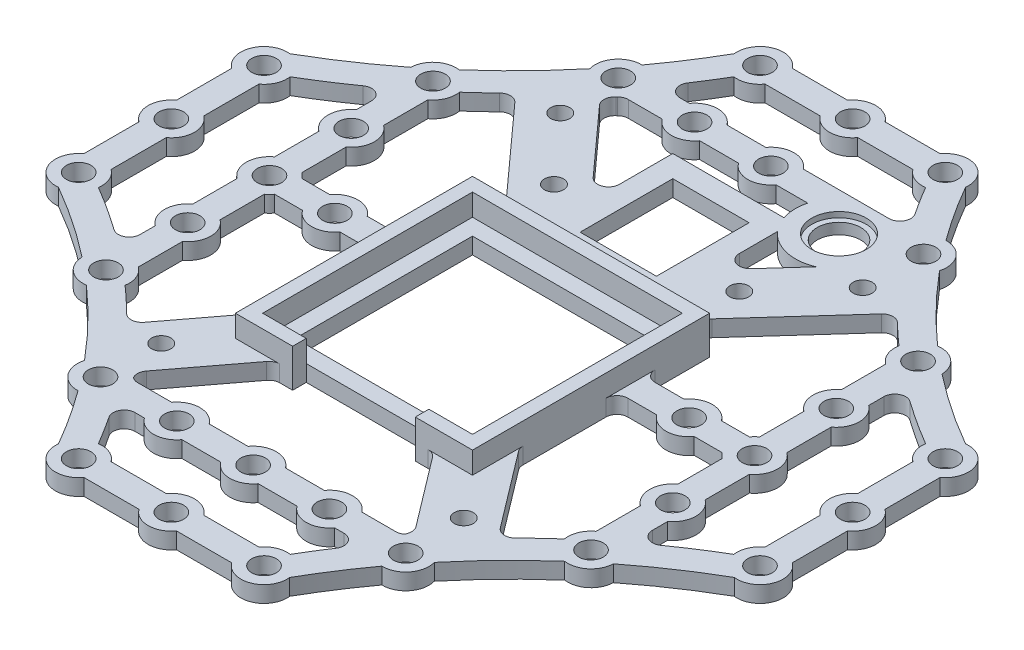
SolidWorks part; units mm, degrees
ref_plane "Front Plane" through (0, 0, 0) normal (0, 0, 1) x (1, 0, 0)
ref_plane "Top Plane" through (0, 0, 0) normal (0, 1, 0) x (1, 0, 0)
ref_plane "Right Plane" through (0, 0, 0) normal (1, 0, 0) x (0, 0, -1)
sketch "Sketch1" plane through (0, 0, 0) normal (0, 1, 0) x (1, 0, 0)
  line L0 (-32, 0) -> (32, 0) construction
  line L1 (-32, 41) -> (32, 41)
  line L2 (-32, 41) -> (-32, -41)
  line L3 (-32, -41) -> (32, -41)
  line L4 (32, 41) -> (32, -41)
  line L5 (-32, 41) -> (32, -41) construction
  line L6 (-32, -41) -> (32, 41) construction
  line L7 (0, 41) -> (0, -41) construction
  circle A0 centre (27.75, -36.6) radius 1.75
  circle A1 centre (-27.75, -36.6) radius 1.75
  circle A2 centre (27.75, 36.6) radius 1.75
  circle A3 centre (-27.75, 36.6) radius 1.75
  point P0 (0, 0)
  dimension "D3" = 3.5
  dimension "D1" = 64
  dimension "D2" = 82
  dimension "D4" = 27.75
  dimension "D5" = 36.6
extrude "Boss-Extrude1" add sketch "Sketch1" along normal blind 3
sketch "Sketch2" plane through (0, 3, 0) normal (0, 1, 0) x (1, 0, 0)
  line L0 (0, 41) -> (0, -41) construction
  line L1 (32, 41) -> (-32, 41) construction
  line L2 (-32, -41) -> (32, -41) construction
  line L3 (-32, 0) -> (32, 0) construction
  line L4 (-32, 41) -> (-32, -41) construction
  line L5 (32, -41) -> (32, 41) construction
  line L6 (-11.25, -26.5) -> (-11.25, -29)
  line L7 (-19.25, 12) -> (19.25, 12)
  line L8 (-19.25, 12) -> (-19.25, -26.5)
  line L9 (-19.25, -26.5) -> (-11.25, -26.5)
  line L10 (19.25, 12) -> (19.25, -26.5)
  line L11 (-19.25, 12) -> (19.25, -26.5) construction
  line L12 (-19.25, -26.5) -> (19.25, 12) construction
  line L13 (-21.75, 14.5) -> (21.75, 14.5)
  line L14 (-21.75, 14.5) -> (-21.75, -29)
  line L15 (-21.75, -29) -> (-11.25, -29)
  line L16 (21.75, 14.5) -> (21.75, -29)
  line L17 (-21.75, 14.5) -> (21.75, -29) construction
  line L18 (-21.75, -29) -> (21.75, 14.5) construction
  line L19 (11.25, -26.5) -> (11.25, -29)
  line L20 (11.25, -26.5) -> (19.25, -26.5)
  line L21 (11.25, -29) -> (21.75, -29)
  point P12 (0, -7.25)
  point P17 (0, -7.25)
  point P19 (0, -7.25)
  dimension "D1" = 38.5
  dimension "D2" = 2.5
  dimension "D3" = 12
  dimension "D4" = 8
  dimension "D5" = 8
extrude "GPS-Housing" add sketch "Sketch2" along normal blind 4
sketch "Sketch3" plane through (0, 3, 0) normal (0, 1, 0) x (1, 0, 0)
  line L0 (-32, 24.7) -> (32, 24.7) construction
  line L1 (-32, 41) -> (-32, -41) construction
  line L2 (32, -41) -> (32, 41) construction
  line L3 (0, 41) -> (0, 6.6316) construction
  line L6 (21.75, 14.5) -> (-21.75, 14.5) construction
  line L7 (32, 41) -> (-32, 41) construction
  circle A0 centre (-17, 24.7) radius 1.75
  circle A1 centre (17, 24.7) radius 1.75
  dimension "D1" = 3.5
  dimension "D2" = 10.2
  dimension "D3" = 17
extrude "Spectrum-Cover-Hole" cut sketch "Sketch3" against normal through all
sketch "Sketch6" plane through (0, 3, 0) normal (0, 1, 0) x (1, 0, 0)
  line L0 (0, 41) -> (0, -41) construction
  line L1 (32, 41) -> (-32, 41) construction
  line L2 (-32, -41) -> (32, -41) construction
  line L3 (-32, 0) -> (32, 0) construction
  line L4 (-32, 41) -> (-32, -41) construction
  line L5 (32, -41) -> (32, 41) construction
  line L6 (0, 0) -> (116.6726, -116.6726) construction
  line L7 (0, -41) -> (0, -155.7646) construction
  line L8 (32, 0) -> (119.0429, 0) construction
  line L9 (65, 19.5647) -> (65, -19.5647)
  line L10 (-19.5647, -65) -> (19.5647, -65)
  line L11 (-65, 19.5647) -> (-65, -19.5647)
  line L12 (-19.5647, 65) -> (19.5647, 65)
  line L14 (-32, 41) -> (32, 41)
  line L15 (32, 41) -> (32, -41)
  line L16 (32, -41) -> (-32, -41)
  line L17 (-32, -41) -> (-32, 41)
  arc A0 (65, -19.5647) -> (19.5647, -65) centre (116.6726, -116.6726) ccw
  circle A1 centre (116.6726, -116.6726) radius 110 construction
  arc A2 (-65, -19.5647) -> (-19.5647, -65) centre (-116.6726, -116.6726) cw
  arc A3 (65, 19.5647) -> (19.5647, 65) centre (116.6726, 116.6726) cw
  arc A4 (-65, 19.5647) -> (-19.5647, 65) centre (-116.6726, 116.6726) ccw
  point P24 (0, -65)
  point P28 (116.6726, -116.6726)
  point P30 (65, 0)
  point P36 (-65, 0)
  dimension "D9" = 220
  dimension "D1" = 45
  dimension "D2" = 65
  dimension "D3" = 65
  dimension "D4" = 165
extrude "Extension" add sketch "Sketch6" against normal blind 3
sketch "Sketch7" plane through (0, 3, 0) normal (0, 1, 0) x (1, 0, 0)
  line L1 (65, 0) -> (-65, 0) construction
  line L2 (65, -19.5647) -> (65, 19.5647) construction
  line L3 (-65, 19.5647) -> (-65, -19.5647) construction
  line L4 (0, 65) -> (0, -65) construction
  line L5 (19.5647, 65) -> (-19.5647, 65) construction
  line L6 (-19.5647, -65) -> (19.5647, -65) construction
  line L8 (0, -60) -> (16.6066, -60)
  line L9 (60, -19.5647) -> (60, 19.5647)
  line L10 (60, -16.6066) -> (60, 0)
  line L11 (-60, 0) -> (-60, -16.6066)
  line L12 (-16.6066, -60) -> (0, -60)
  line L13 (0, 60) -> (-16.6066, 60)
  line L14 (-60, 16.6066) -> (-60, 0)
  line L15 (60, 0) -> (60, 16.6066)
  line L16 (16.6066, 60) -> (0, 60)
  line L18 (47, 25.1809) -> (47, -25.1809)
  line L19 (42, 29.2141) -> (42, -29.2141)
  line L20 (21.75, -20.4107) -> (34.0707, -36.6606)
  line L21 (60, 2.5) -> (60, -2.5)
  line L24 (0, 0) -> (27.75, -36.6) construction
  line L25 (21.75, -29) -> (21.75, 14.5) construction
  line L26 (14.608, -29) -> (26.7391, -45)
  line L27 (11.25, -29) -> (21.75, -29) construction
  line L28 (-22.9722, -50) -> (22.9722, -50)
  line L29 (-26.7391, -45) -> (26.7391, -45)
  line L30 (-10.8771, 43.5) -> (12.4237, 43.5) construction
  line L31 (21.75, 14.5) -> (-21.75, 14.5) construction
  line L32 (-47, 25.1809) -> (-47, -25.1809)
  line L33 (-42, 29.2141) -> (-42, -29.2141)
  line L34 (-21.75, -20.4107) -> (-34.0707, -36.6606)
  line L35 (-14.608, -29) -> (-26.7391, -45)
  line L36 (15.8714, 14.5) -> (35.0176, 35.6944)
  line L37 (-15.8714, 14.5) -> (-35.0176, 35.6944)
  line L38 (-22.9722, 50) -> (22.9722, 50)
  line L39 (-7, 36.5) -> (7, 36.5)
  line L40 (-7, 36.5) -> (-7, 19.5)
  line L41 (-7, 19.5) -> (7, 19.5)
  line L42 (7, 36.5) -> (7, 19.5)
  line L43 (-7, 36.5) -> (7, 19.5) construction
  line L44 (-7, 19.5) -> (7, 36.5) construction
  line L45 (-26.7391, 45) -> (26.7391, 45)
  line L46 (-19.25, 12) -> (19.25, 12) construction
  line L47 (-16.25, 9) -> (16.25, 9)
  line L48 (-16.25, 9) -> (-16.25, -23.5)
  line L49 (-16.25, -23.5) -> (-11.25, -23.5)
  line L50 (16.25, 9) -> (16.25, -23.5)
  line L51 (-19.25, -26.5) -> (-19.25, 12) construction
  line L52 (19.25, 12) -> (19.25, -26.5) construction
  line L53 (19.25, -26.5) -> (11.25, -26.5) construction
  line L54 (-11.25, -29) -> (-11.25, -23.5)
  line L55 (11.25, -29) -> (11.25, -23.5)
  line L57 (11.25, -23.5) -> (16.25, -23.5)
  line L58 (-21.75, 14.5) -> (-21.75, -29) construction
  line L59 (-42, 2.5) -> (-21.75, 2.5)
  line L60 (-42, 2.5) -> (-42, -2.5)
  line L61 (-42, -2.5) -> (-21.75, -2.5)
  line L62 (-21.75, 2.5) -> (-21.75, -2.5)
  line L63 (42, -2.5) -> (21.75, -2.5)
  line L64 (42, 2.5) -> (21.75, 2.5)
  line L65 (21.75, 14.5) -> (-21.75, 14.5) construction
  line L66 (27.75, 36.6) -> (17, 24.7) construction
  line L67 (15.8714, 14.5) -> (21.75, 14.5)
  line L68 (21.75, 14.5) -> (21.75, 2.5)
  line L69 (-15.8714, 14.5) -> (-21.75, 14.5)
  line L70 (-21.75, 14.5) -> (-21.75, 2.5)
  line L71 (-11.25, -23.5) -> (11.25, -23.5)
  line L72 (-11.25, -26.5) -> (11.25, -26.5)
  arc A6 (62.6512, -15.1507) -> (15.1507, -62.6512) centre (116.6726, -116.6726) ccw
  arc A7 (60, -16.6066) -> (16.6066, -60) centre (116.6726, -116.6726) ccw
  arc A8 (-16.6066, -60) -> (-60, -16.6066) centre (-116.6726, -116.6726) ccw
  arc A9 (-60, 16.6066) -> (-16.6066, 60) centre (-116.6726, 116.6726) ccw
  arc A10 (16.6066, 60) -> (60, 16.6066) centre (116.6726, 116.6726) ccw
  point P45 (0, 0)
  point P73 (0, 28)
  line M3 (21.75, 14.5) -> (21.75, -29)
  line M4 (21.75, -29) -> (11.25, -29)
  line M5 (11.25, -29) -> (11.25, -26.5)
  line M11 (-11.25, -26.5) -> (-11.25, -29)
  line M12 (-11.25, -29) -> (-21.75, -29)
  line M13 (-21.75, -29) -> (-21.75, 14.5)
  line M20 (-21.75, 14.5) -> (21.75, 14.5)
  dimension "D1" = 5
  dimension "D4" = 2.5
  dimension "D2" = 42
  dimension "D3" = 5
  dimension "D5" = 10
  dimension "D8" = 5
  dimension "D10" = 5
  dimension "D11" = 29
  dimension "D12" = 5
  dimension "D13" = 7
  dimension "D14" = 14
  dimension "D15" = 5
  dimension "D16" = 10
  dimension "D17" = 3
  dimension "D18" = 3
  dimension "D19" = 3
  dimension "D20" = 3
  dimension "D21" = 2.5
  dimension "D22" = 6
  dimension "D6" = 5
  dimension "D7" = 5
  dimension "D9" = 4
extrude "Weight-Reducer" cut sketch "Sketch7" against normal through all contours A10 L16 L13 A9 L38 | A10 L18 A7 L10 L15 | A8 L12 L8 A7 L28 | A9 L14 L11 A8 L32 | L42 L39 L40 L41 | L55 L57 L50 L47 L48 L49 L54 L35 L29 L26 M11 M12 M4 M5 | A8 L34 L61 L33 M13 | A7 L19 L63 L20 M3 | A10 L36 L64 L19 M20 M3 | A9 L33 L59 L37 M13 M20 | L49 L71 L57 L50 L47 L48 region at (0, 3, 54.7305) region at (0, 3, 36.9962) region at (32.5447, 3, 16.7096) region at (-32.5447, 3, 16.7096) region at (53.0515, 3, 0) region at (-53.0515, 3, 0) region at (0, 3, 7.25) region at (32.1272, 3, -16.4309) region at (-32.1272, 3, -16.4309) region at (0, 3, -54.7305) region at (0, 3, -28)
sketch "Sketch8" plane through (0, 3, 0) normal (0, 1, 0) x (1, 0, 0)
  line L1 (0, 0) -> (0, 68.176) construction
  line L2 (-77.2406, 0) -> (92.1007, 0) construction
  circle A0 centre (17, 43) radius 4
  point P7 (-17, 43)
  point P8 (14.4616, 43)
  dimension "D1" = 8
  dimension "D2" = 17
  dimension "D3" = 43
extrude "Arm-Button-Hole" cut sketch "Sketch8" against normal through all
sketch "Sketch9" plane through (0, 3, 0) normal (0, 1, 0) x (1, 0, 0)
  circle A0 centre (17, 43) radius 5
  dimension "D1" = 10
extrude "Arm-Button-Hole-LG" cut sketch "Sketch9" against normal blind 1
sketch "Sketch11" plane through (0, 3, 0) normal (0, 1, 0) x (1, 0, 0)
  line L0 (-27.75, 36.6) -> (-17, 24.7) construction
  line L1 (-27.6172, 43.9119) -> (-11, 25.517)
  line L2 (-11, 25.517) -> (-11, 40.5)
  line L3 (-11, 40.5) -> (9.4007, 40.5)
  line L4 (-26.7391, 45) -> (9.254, 45)
  line L5 (27.75, 36.6) -> (17, 24.7) construction
  line L6 (-22.9722, 50) -> (22.9722, 50) construction
  line L7 (-7, 36.5) -> (7, 36.5) construction
  line L8 (-7, 36.5) -> (-7, 19.5) construction
  line L9 (11, 37.7085) -> (11, 25.517)
  line L10 (11, 25.517) -> (20.1506, 35.6465)
  line L11 (7, 36.5) -> (7, 19.5) construction
  arc A2 (-62.6512, 15.1507) -> (-15.1507, 62.6512) centre (-116.6726, 116.6726) ccw
  arc A3 (-27.6172, 43.9119) -> (-26.7391, 45) centre (-116.6726, 116.6726) ccw
  arc A4 (11, 37.7085) -> (20.1506, 35.6465) centre (17, 43) ccw
  circle A5 centre (17, 43) radius 8
  arc A6 (9.254, 45) -> (9.4007, 40.5) centre (17, 43) ccw
  dimension "D2" = 5
  dimension "D3" = 5
  dimension "D4" = 4
  dimension "D5" = 4
  dimension "D7" = 4
  dimension "D8" = 5
  dimension "D1" = 5
  dimension "D6" = 3
extrude "Weight-Reducer2" cut sketch "Sketch11" against normal through all
sketch "Sketch12" plane through (0, 3, 0) normal (0, 1, 0) x (1, 0, 0)
  line L0 (-65, 0) -> (65, 0) construction
  line L3 (0, 65) -> (0, -65) construction
  line L4 (19.5647, 65) -> (-19.5647, 65) construction
  line L5 (-19.5647, -65) -> (19.5647, -65) construction
  line L6 (-65, 19.5647) -> (-65, -19.5647) construction
  line L8 (65, -19.5647) -> (65, 19.5647) construction
  line L9 (62.5, 27.8761) -> (62.5, -28.3487) construction
  line L10 (44.5, 40.0562) -> (44.5, -38.8909) construction
  line L11 (47, 25.1809) -> (47, -25.1809) construction
  line L12 (-43.7279, -47.5) -> (38.8791, -47.5) construction
  line L13 (-26.7391, -45) -> (26.7391, -45) construction
  circle A0 centre (62.5, 0) radius 2.25
  circle A1 centre (62.5, 17) radius 2.25
  circle A2 centre (62.5, -17) radius 2.25
  circle A3 centre (44.5, 30) radius 2.25
  circle A4 centre (44.5, 15) radius 2.25
  circle A5 centre (44.5, 0) radius 2.25
  circle A6 centre (44.5, -15) radius 2.25
  circle A7 centre (44.5, -30) radius 2.25
  circle A8 centre (32.5, 0) radius 2.25
  circle A9 centre (0, -47.5) radius 2.25
  circle A10 centre (-14, -47.5) radius 2.25
  circle A11 centre (-28, -47.5) radius 2.25
  circle A12 centre (14, -47.5) radius 2.25
  circle A13 centre (28, -47.5) radius 2.25
  circle A14 centre (28, 47.5) radius 2.25
  circle A15 centre (-17, -62.5) radius 2.25
  circle A16 centre (0, -62.5) radius 2.25
  circle A17 centre (17, -62.5) radius 2.25
  circle A18 centre (-32.5, 0) radius 2.25
  circle A19 centre (-44.5, 0) radius 2.25
  circle A20 centre (-44.5, -15) radius 2.25
  circle A21 centre (-44.5, -30) radius 2.25
  circle A22 centre (-44.5, 15) radius 2.25
  circle A23 centre (-44.5, 30) radius 2.25
  circle A24 centre (-62.5, 17) radius 2.25
  circle A25 centre (-62.5, 0) radius 2.25
  circle A26 centre (-62.5, -17) radius 2.25
  circle A28 centre (0, 47.5) radius 2.25
  circle A29 centre (-14, 47.5) radius 2.25
  circle A30 centre (-28, 47.5) radius 2.25
  circle A33 centre (17, 62.5) radius 2.25
  circle A34 centre (0, 62.5) radius 2.25
  circle A35 centre (-17, 62.5) radius 2.25
  circle A36 centre (0, 32.5) radius 2.25 [skipped]
  circle A37 centre (0, -32.5) radius 2.25 [skipped]
  circle A38 centre (-30, -44.5) radius 2.25 [skipped]
  circle A39 centre (-15, -44.5) radius 2.25 [skipped]
  circle A40 centre (0, -44.5) radius 2.25 [skipped]
  circle A41 centre (15, -44.5) radius 2.25 [skipped]
  circle A42 centre (30, -44.5) radius 2.25 [skipped]
  circle A43 centre (-30, 44.5) radius 2.25 [skipped]
  circle A44 centre (-15, 44.5) radius 2.25 [skipped]
  circle A45 centre (0, 44.5) radius 2.25 [skipped]
  circle A46 centre (15, 44.5) radius 2.25 [skipped]
  circle A47 centre (30, 44.5) radius 2.25 [skipped]
  point P14 (62.5, 0)
  point P94 (0, 0)
  dimension "D2" = 4.5
  dimension "D3" = 4.5
  dimension "D6" = 4.5
  dimension "D7" = 4.5
  dimension "D8" = 4.5
  dimension "D11" = 4.5
  dimension "D15" = 4.5
  dimension "D16" = 4.5
  dimension "D17" = 4.5
  dimension "D1" = 2.5
  dimension "D4" = 17
  dimension "D5" = 2.5
  dimension "D9" = 15
  dimension "D10" = 30
  dimension "D12" = 12
  dimension "D14" = 2.5
  dimension "D18" = 14
  dimension "D19" = 28
  dimension "D13" = 4
extrude "Marker-Holes" cut sketch "Sketch12" against normal through all
sketch "Sketch13" plane through (0, 3, 0) normal (0, 1, 0) x (1, 0, 0)
  line L4 (-65, 0) -> (62.5, 0) construction
  line L5 (-65, 19.5647) -> (-65, -19.5647) construction
  line L6 (0, 62.5) -> (0, -62.5) construction
  circle A0 centre (62.5, 0) radius 4.25
  circle A1 centre (62.5, 0) radius 2.25 construction
  circle A2 centre (62.5, 17) radius 4.25
  circle A3 centre (62.5, 17) radius 2.25 construction
  circle A4 centre (62.5, 17) radius 2.25
  circle A5 centre (62.5, -17) radius 2.25
  circle A6 centre (62.5, -17) radius 4.25
  circle A7 centre (44.5, 30) radius 4.25
  circle A8 centre (44.5, 30) radius 2.25 construction
  circle A9 centre (44.5, 30) radius 2.25
  circle A10 centre (44.5, 15) radius 4.25
  circle A11 centre (44.5, 15) radius 2.25
  circle A12 centre (44.5, 0) radius 4.25
  circle A13 centre (44.5, 0) radius 2.25
  circle A14 centre (44.5, -15) radius 4.25
  circle A15 centre (44.5, -15) radius 2.25
  circle A16 centre (44.5, -30) radius 4.25
  circle A17 centre (44.5, -30) radius 2.25
  circle A18 centre (32.5, 0) radius 4.25
  circle A19 centre (32.5, 0) radius 2.25 construction
  circle A20 centre (32.5, 0) radius 2.25
  circle A21 centre (62.5, 0) radius 2.25
  circle A22 centre (17, -62.5) radius 4.25
  circle A23 centre (17, -62.5) radius 2.25
  circle A24 centre (0, -62.5) radius 2.25
  circle A25 centre (0, -62.5) radius 4.25
  circle A26 centre (-17, -62.5) radius 2.25
  circle A27 centre (-17, -62.5) radius 4.25
  circle A28 centre (-62.5, -17) radius 4.25
  circle A29 centre (-62.5, -17) radius 2.25
  circle A30 centre (-62.5, 0) radius 2.25
  circle A31 centre (-62.5, 0) radius 4.25
  circle A32 centre (-62.5, 17) radius 2.25
  circle A33 centre (-62.5, 17) radius 4.25
  circle A34 centre (-17, 62.5) radius 4.25
  circle A35 centre (-17, 62.5) radius 2.25
  circle A36 centre (0, 62.5) radius 2.25
  circle A37 centre (0, 62.5) radius 4.25
  circle A38 centre (17, 62.5) radius 2.25
  circle A39 centre (17, 62.5) radius 4.25
  circle A40 centre (-32.5, 0) radius 2.25
  circle A41 centre (-32.5, 0) radius 4.25
  circle A42 centre (-44.5, -30) radius 2.25
  circle A43 centre (-44.5, -30) radius 4.25
  circle A44 centre (-44.5, -15) radius 2.25
  circle A45 centre (-44.5, -15) radius 4.25
  circle A46 centre (-44.5, 0) radius 2.25
  circle A47 centre (-44.5, 0) radius 4.25
  circle A48 centre (-44.5, 15) radius 2.25
  circle A49 centre (-44.5, 15) radius 4.25
  circle A50 centre (-44.5, 30) radius 2.25
  circle A51 centre (-44.5, 30) radius 4.25
  circle A52 centre (-28, -47.5) radius 4.25
  circle A53 centre (-28, -47.5) radius 2.25 construction
  circle A54 centre (-28, -47.5) radius 2.25
  circle A55 centre (-14, -47.5) radius 4.25
  circle A56 centre (-14, -47.5) radius 2.25
  circle A57 centre (0, -47.5) radius 4.25
  circle A58 centre (0, -47.5) radius 2.25
  circle A59 centre (14, -47.5) radius 4.25
  circle A60 centre (14, -47.5) radius 2.25
  circle A61 centre (28, -47.5) radius 4.25
  circle A62 centre (28, -47.5) radius 2.25
  circle A63 centre (28, 47.5) radius 2.25
  circle A64 centre (28, 47.5) radius 4.25
  circle A65 centre (0, 47.5) radius 4.25
  circle A66 centre (0, 47.5) radius 2.25
  circle A67 centre (-14, 47.5) radius 2.25
  circle A68 centre (-14, 47.5) radius 4.25
  circle A69 centre (-28, 47.5) radius 2.25
  circle A70 centre (-28, 47.5) radius 4.25
  point P73 (0, 0)
  dimension "D1" = 8.5
  dimension "D2" = 8.5
  dimension "D3" = 8.5
  dimension "D5" = 8.5
  dimension "D7" = 8.5
  dimension "D4" = 5
  dimension "D8" = 5
  dimension "D6" = 4
extrude "Boss-Extrude3" add sketch "Sketch13" against normal blind 3
fillet "Fillet1" radius 2 30 edges at (11, 1.5, -25.517) (-11, 1.5, -25.517) (-24.5631, 1.5, -45) (-27.1053, 1.5, -43.3452) (24.5631, 1.5, 45) (25.8535, 1.5, 43.8319) (-24.5631, 1.5, 45) (-25.8535, 1.5, 43.8319) (22.9722, 1.5, 50) (-22.9722, 1.5, 50) (22.9722, 1.5, -50) (-22.9722, 1.5, -50) (21.75, 1.5, 2.5) (21.75, 1.5, -2.5) (-21.75, 1.5, 2.5) (-21.75, 1.5, -2.5) (47, 1.5, 25.1809) (-47, 1.5, 25.1809) (-47, 1.5, -25.1809) (47, 1.5, -25.1809) (-34.0707, 1.5, 36.6606) (34.0707, 1.5, 36.6606) (-35.0176, 1.5, -35.6944) (-21.75, 1.5, 20.4107) (-14.608, 1.5, 29) (14.608, 1.5, 29) (21.75, 1.5, 20.4107) (-15.8714, 1.5, -14.5) (15.8714, 1.5, -14.5) (35.0176, 1.5, -35.6944)
